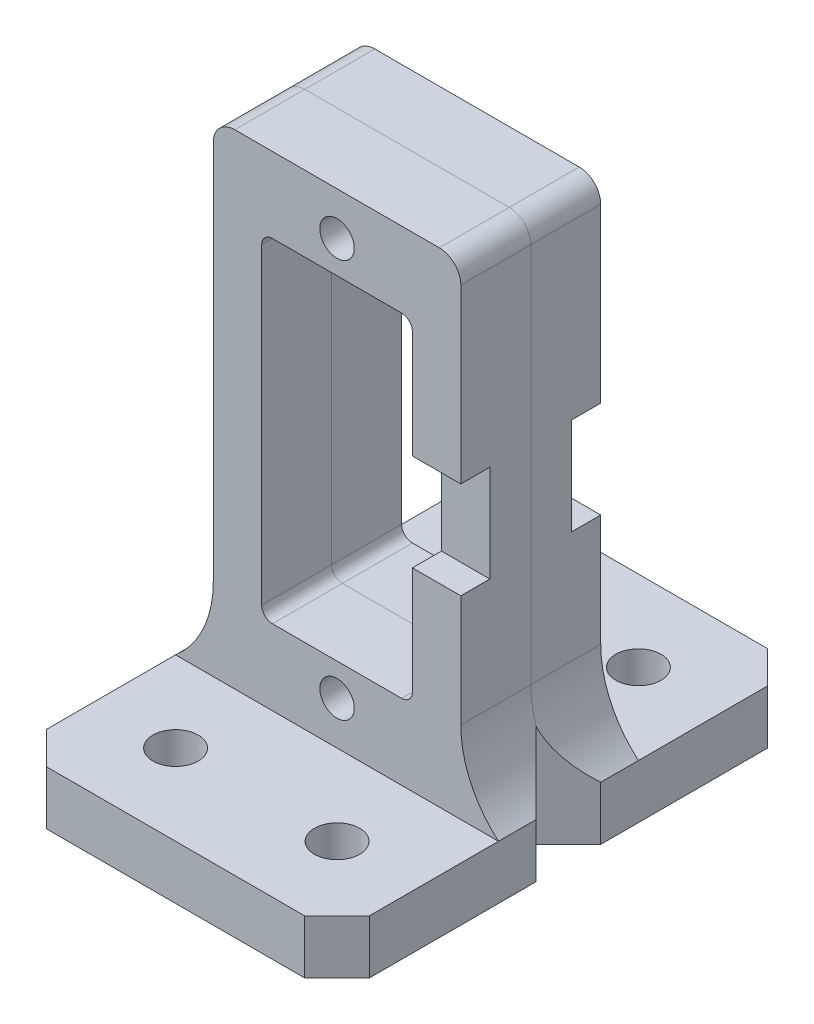
SolidWorks part; units mm, degrees
ref_plane "前基準面" through (0, 0, 0) normal (0, 0, 1) x (1, 0, 0)
ref_plane "上基準面" through (0, 0, 0) normal (0, 1, 0) x (1, 0, 0)
ref_plane "右基準面" through (0, 0, 0) normal (1, 0, 0) x (0, 0, -1)
sketch "草圖1" plane through (0, 0, 0) normal (0, 0, 1) x (1, 0, 0)
  line L1 (7, -15.5) -> (-7, -15.5)
  line L2 (7, -15.5) -> (7, 15.5)
  line L3 (7, 15.5) -> (-7, 15.5)
  line L4 (-7, -15.5) -> (-7, 15.5)
  line L5 (7, -15.5) -> (-7, 15.5) construction
  line L6 (7, 15.5) -> (-7, -15.5) construction
  line L8 (11.5, -22.5) -> (11.5, 22.5)
  line L9 (11.5, 22.5) -> (-11.5, 22.5)
  line L10 (-11.5, -22.5) -> (-11.5, 22.5)
  line L11 (11.5, -22.5) -> (-11.5, 22.5) construction
  line L12 (11.5, 22.5) -> (-11.5, -22.5) construction
  line L13 (15, -27.5) -> (-15, -27.5)
  line L17 (-15, -27.5) -> (-15, -22.5)
  line L18 (-15, -22.5) -> (-11.5, -22.5)
  line L19 (11.5, -22.5) -> (15, -22.5)
  line L20 (15, -22.5) -> (15, -27.5)
  point P0 (0, 0)
  point P6 (0, 0)
  dimension "D1" = 31
  dimension "D2" = 45
  dimension "D3" = 23
  dimension "D4" = 14
  dimension "D5" = 5
  dimension "D6" = 3.5
  dimension "D7" = 30
extrude "填料-伸長1" add sketch "草圖1" along normal blind 6.5 contours L10 L8 L9 L1 L4 L3 L2 | L13 | L13 region at (13.25, -23.0831, 0)
sketch "草圖2" plane through (0, 0, 6.5) normal (0, 0, 1) x (1, 0, 0)
  line L0 (-15, -22.5) -> (15, -22.5)
  line L1 (15, -27.5) -> (-15, -27.5) construction
  line L3 (-15, -27.5) -> (-15, -22.5) construction
  line L6 (-15, -27.5) -> (15, -27.5)
  line L8 (-15, -27.5) -> (-15, -22.5)
  line L9 (15, -27.5) -> (15, -22.5)
  dimension "D3" = 30
extrude "填料-伸長2" add sketch "草圖2" along normal blind 15 contours L9 L0 L8 L6
sketch "草圖3" plane through (0, 0, 6.5) normal (0, 0, 1) x (1, 0, 0)
  line L0 (11.5, -22.5) -> (11.5, 22.5) construction
  line L1 (7, -4.5) -> (11.5, -4.5)
  line L2 (7, -4.5) -> (7, 4.5)
  line L3 (7, 4.5) -> (11.5, 4.5)
  line L4 (11.5, -4.5) -> (11.5, 4.5)
  line L5 (7, -4.5) -> (11.5, 4.5) construction
  line L6 (7, 4.5) -> (11.5, -4.5) construction
  line L7 (7, -15.5) -> (7, 15.5) construction
  line L8 (11.5, 22.5) -> (-11.5, 22.5) construction
  point P0 (9.25, 0)
  dimension "D1" = 0
  dimension "D2" = 9
  dimension "D3" = 18
extrude "除料-伸長1" cut sketch "草圖3" against normal blind 2.7
sketch "草圖4" plane through (0, 0, 6.5) normal (0, 0, 1) x (1, 0, 0)
  line L0 (11.5, 22.5) -> (-11.5, 22.5) construction
  line L1 (-11.5, -22.5) -> (-11.5, 22.5) construction
  circle A0 centre (0, 18.5) radius 1.6
  dimension "D1" = 3.2
  dimension "D2" = 4
  dimension "D3" = 11.5
extrude "除料-伸長2" cut sketch "草圖4" against normal through all
pattern_linear "直線複製排列1" count 2 spacing 37 along (0, -1, 0) of "除料-伸長2"
sketch "草圖5" plane through (0, -22.5, 0) normal (0, 1, 0) x (1, 0, 0)
  line L5 (15, 0) -> (15, -21.5) construction
  line L6 (-15, -21.5) -> (15, -21.5) construction
  circle A0 centre (-7.5, -14) radius 2.1
  circle A2 centre (7.5, -14) radius 2.1
  dimension "D1" = 4.2
  dimension "D2" = 7.5
  dimension "D3" = 7.5
  dimension "D4" = 4.2
  dimension "D7" = 15
extrude "除料-伸長3" cut sketch "草圖5" against normal through all contours A0 | A0 | A2 | A2 | A2 region at (-7.5, -22.5, 14) region at (7.5, -22.5, 14)
fillet "圓角2" radius 2 2 edges at (11.5, 22.5, 3.25) (-11.5, 22.5, 3.25)
fillet "圓角3" radius 10 2 edges at (-11.5, -22.5, 3.25) (11.5, -22.5, 3.25)
chamfer "導角1" distance 3 angle 45 4 edges at (15, -25, 21.5) (-15, -25, 21.5) (-15, -25, 0) (15, -25, 0)
fillet "圓角4" radius 1 4 edges at (7, -15.5, 3.25) (-7, -15.5, 3.25) (-7, 15.5, 3.25) (7, 15.5, 3.25)
ref_plane "平面1" through (0, 0, 0) normal (0, 0, -1) x (-1, 0, 0)
mirror "鏡射2" about plane through (0, 0, 0) normal (0, 0, -1) of bodies 110
split "分割1" trim tools "平面1" bodies to split 112 resulting bodies 113 114
